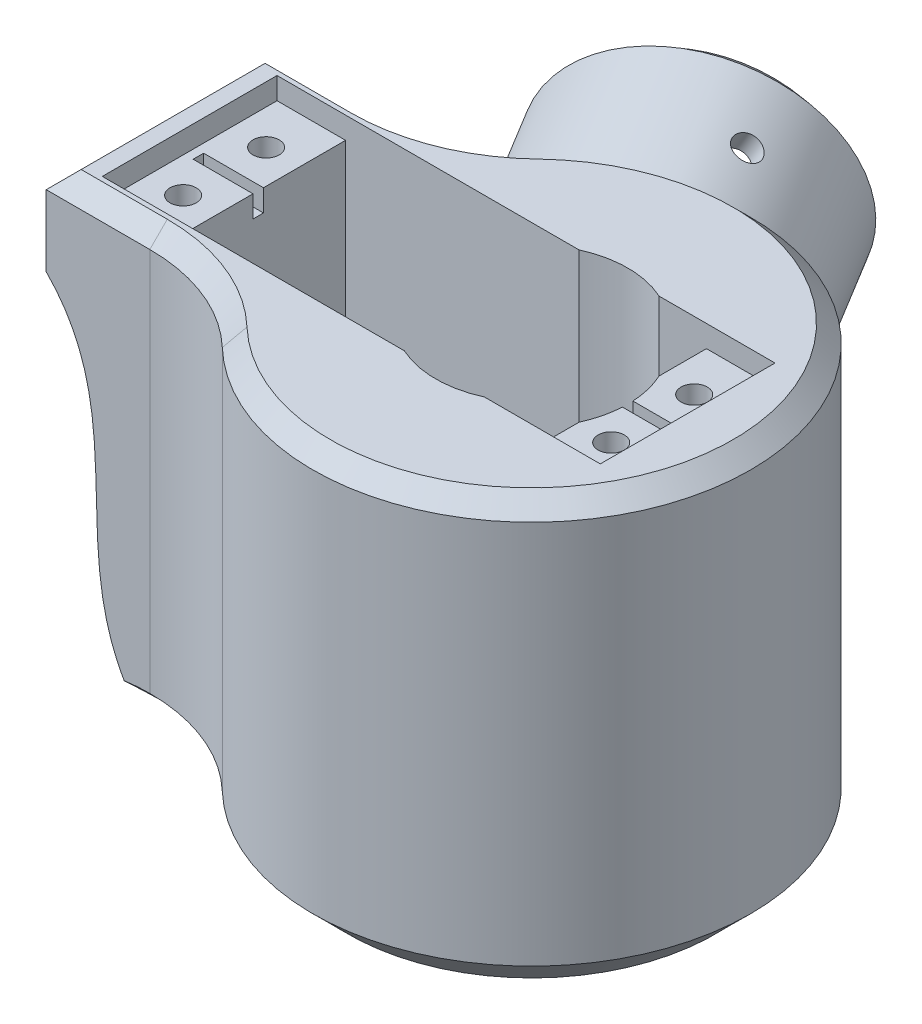
SolidWorks part; units mm, degrees
material "Melamine resin"
ref_plane "Front Plane" through (0, 0, 0) normal (0, 0, 1) x (1, 0, 0)
ref_plane "Top Plane" through (0, 0, 0) normal (0, 1, 0) x (1, 0, 0)
ref_plane "Right Plane" through (0, 0, 0) normal (1, 0, 0) x (0, 0, -1)
sketch "Sketch1" plane through (0, 0, 0) normal (0, 1, 0) x (1, 0, 0)
  line L0 (-37, -12.5248) -> (-25.1408, -12.5248)
  line L1 (-37, -12.5248) -> (-37, 12.5248)
  line L2 (-37, 12.5248) -> (-25.1408, 12.5248)
  arc A0 (-11.2801, -18.0914) -> (-25.1408, -12.5248) centre (-25.1408, -32.5646) ccw
  arc A1 (-25.1408, 12.5248) -> (-11.2801, 18.0914) centre (-25.1408, 32.5646) ccw
  arc A2 (-11.2801, -18.0914) -> (-11.2801, 18.0914) centre (6.0458, 0) ccw
  dimension "D2" = 20.0397
  dimension "D3" = 25.0497
  dimension "D1" = 37
  dimension "D4" = 6.0458
extrude "Boss-Extrude2" add sketch "Sketch1" along normal blind 50
ref_axis "Axis1" through (6.0458, 50, 0) along (0, -1, 0)
ref_point "Point1"
ref_plane "Plane1" through (0, 25, 0) normal (0, 1, 0) x (1, 0, 0)
sketch "Sketch2" plane through (0, 25, 0) normal (0, 1, 0) x (1, 0, 0)
  point P0 (6.0458, 0)
sketch3d "3DSketch2"
  line L0 (6.0458, 25, 0) -> (-125.4586, 70.8173, -246.2467)
chamfer "Chamfer1" distance 2 angle 45 5 edges at (-17.6724, 50, 13.9685) (-17.6724, 50, -13.9685) (31.0955, 50, 0) (-31.0704, 50, 12.5248) (-31.0704, 50, -12.5248)
sketch3d "3DSketch1"
  line L0 (6.0458, 25, 0) -> (-9.6875, 5.6459, 90)
  line L1 (6.0338, 25, 0) -> (-25.4087, -13.7083, 180) construction
ref_plane "Plane2" through (6.0458, 25, 0) normal (-0.4649, 0.162, -0.8705) x (-0.8854, -0.0758, 0.4587)
sketch "Sketch3" plane through (6.0458, 25, 0) normal (-0.4649, 0.162, -0.8705) x (-0.8854, -0.0758, 0.4587)
  circle A0 centre (0, 0) radius 15
  dimension "D1" = 30
extrude "Boss-Extrude3" add sketch "Sketch3" along normal blind 50
sketch "Sketch5" plane through (-23.8183, 8.2985, -44.6006) normal (-0.4649, 0.162, -0.8705) x (-0.8767, -0.2212, 0.4271)
  circle A0 centre (-10.8312, 23.296) radius 12.7
  dimension "D1" = 25.4
extrude "Cut-Extrude1" cut sketch "Sketch5" against normal blind 21
fillet "Fillet2" radius 3 2 edges at (-16.6363, 28.2884, -10.6306) (-17.5453, 23.9713, -14.02)
chamfer "Chamfer2" distance 3 angle 45 1 edges at (-30.4282, 33.0979, -36.4564)
ref_plane "Plane3" through (-37, 48, -12.5248) normal (0.4917, 0.8648, -0.1017) x (0.8707, -0.4872, 0.0669)
sketch "Sketch6" plane through (-37, 48, -12.5248) normal (0.4917, 0.8648, -0.1017) x (0.8707, -0.4872, 0.0669)
  line L0 (24.0545, 30.2209) -> (44.8977, -2.1034) construction
  line L1 (36.6609, 38.3497) -> (11.448, 22.092) construction
  line L2 (49.5248, -9.2792) -> (-103.7829, 228.4745) construction
  circle A0 centre (28.3898, 23.4975) radius 1.5
  dimension "D1" = 3
  dimension "D2" = 8
extrude "Cut-Extrude2" cut sketch "Sketch6" against normal mid plane 40
ref_point "Point2"
sketch "Sketch7" plane through (0, 0, 0) normal (0, -1, 0) x (-1, 0, 0)
  circle A0 centre (-6.0458, 0) radius 4.125
  dimension "D1" = 8.25
extrude "Cut-Extrude3" cut sketch "Sketch7" against normal blind 117
sketch "Sketch8" plane through (0, 0, 0) normal (0, -1, 0) x (1, 0, 0)
  circle A0 centre (6.0458, 0) radius 11
  dimension "D1" = 22
extrude "Cut-Extrude4" cut sketch "Sketch8" against normal blind 8
sketch "Sketch9" plane through (0, 0, -12.5248) normal (0, 0, -1) x (-1, 0, 0)
  line L0 (37, 48) -> (37, 0) construction
  line L1 (25.1408, 0) -> (37, 0)
  line L2 (37, 0) -> (37, 39.8592)
  line L3 (37, 48) -> (25.1408, 48) construction
  spline S0 degree 3 poles (25.1408, 0) (36.5072, 11.2641) (26.1211, 28.9323) (37, 39.8592) knots 0 0 0 0 1 1 1 1
  dimension "D1" = 4.2177
  dimension "D2" = 6.1294
  dimension "D3" = 8.1408
  dimension "D4" = 15.0833
  dimension "D5" = 34.9044
extrude "Cut-Extrude5" cut sketch "Sketch9" against normal blind 96
chamfer "Chamfer3" distance 2 angle 45 1 edges at (-37, 50, 0)
sketch "Sketch10" plane through (0, 50, 0) normal (0, 1, 0) x (1, 0, 0)
  line L0 (22.894, 0) -> (-44.1666, 0) construction
  line L1 (16.0458, 10) -> (-25.2578, 10)
  line L2 (16.0458, 10) -> (16.0458, -10)
  line L3 (16.0458, -10) -> (-25.2578, -10)
  line L4 (-25.2578, 10) -> (-25.2578, -10)
  line L5 (16.0458, 10) -> (-25.2578, -10) construction
  line L6 (16.0458, -10) -> (-25.2578, 10) construction
  line L7 (-32.106, 10) -> (22.894, 10)
  line L8 (-32.106, 10) -> (-32.106, -10)
  line L9 (-32.106, -10) -> (22.894, -10)
  line L10 (22.894, 10) -> (22.894, -10)
  line L11 (-32.106, 10) -> (22.894, -10) construction
  line L12 (-32.106, -10) -> (22.894, 10) construction
  line L13 (-4.606, 0) -> (-4.606, -13.0522) construction
  line L14 (9.1976, 0.6) -> (22.894, 0.6)
  line L15 (9.1976, 0.6) -> (9.1976, -0.6)
  line L16 (9.1976, -0.6) -> (22.894, -0.6)
  line L17 (22.894, 0.6) -> (22.894, -0.6)
  line L18 (9.1976, 0.6) -> (22.894, -0.6) construction
  line L19 (9.1976, -0.6) -> (22.894, 0.6) construction
  line L20 (-4.606, -13.0522) -> (-4.606, 13.6107) construction
  line L21 (-32.106, 10) -> (-32.106, -10)
  line L22 (-18.4096, 0.6) -> (-18.4096, -0.6)
  line L23 (-18.4096, -0.6) -> (-32.106, -0.6)
  line L24 (-18.4096, 0.6) -> (-32.106, 0.6)
  circle A0 centre (19.894, -4.75) radius 1.5
  circle A1 centre (19.894, 4.75) radius 1.5
  circle A2 centre (-29.106, -4.75) radius 1.5
  circle A3 centre (-29.106, 4.75) radius 1.5
  point P0 (4.5863, -4.4511)
  point P6 (-4.606, 0)
  point P12 (16.0458, 0)
  circle M17 centre (6.0458, 0) radius 4.125
  dimension "D6" = 3
  dimension "D1" = 20
  dimension "D2" = 41.3036
  dimension "D3" = 10
  dimension "D4" = 55
  dimension "D5" = 1.2
  dimension "D7" = 5.25
  dimension "D8" = 3
extrude "Cut-Extrude6" cut sketch "Sketch10" against normal blind 35 contours L24 L22 L23 L4 L3 L2 L16 L14 L1 M17 | L22 L24 L4 L23 | A3 | A2 | L16 L2 L14 M17 | A0 | A1 region at (-5.3362, 50, 0) region at (13.101, 50, 0) region at (-21.8337, 50, 0) region at (19.894, 50, 4.75) region at (19.894, 50, -4.75) region at (-29.106, 50, 4.75) region at (-29.106, 50, -4.75)
sketch "Sketch11" plane through (0, 50, 0) normal (0, 1, 0) x (1, 0, 0)
  line L0 (-35, 10.5248) -> (-35, -10.5248) construction
  line L1 (22.894, -0.6) -> (16.0458, -0.6)
  line L2 (22.894, -0.6) -> (22.894, 0.6)
  line L3 (22.894, 0.6) -> (16.0458, 0.6)
  line L4 (16.0458, -0.6) -> (16.0458, 0.6)
  line L5 (-32.106, -0.6) -> (-25.2578, -0.6)
  line L6 (-32.106, -0.6) -> (-32.106, 0.6)
  line L7 (-32.106, 0.6) -> (-25.2578, 0.6)
  line L8 (-25.2578, -0.6) -> (-25.2578, 0.6)
  line L9 (-25.1408, 10.5248) -> (-35, 10.5248) construction
  dimension "D1" = 9.8592
extrude "Cut-Extrude7" cut sketch "Sketch11" against normal blind 5
sketch "Sketch12" plane through (0, 50, 0) normal (0, 1, 0) x (1, 0, 0)
  line L0 (16.0458, -10) -> (-25.2578, -10) construction
  line L1 (23.894, 10) -> (-33.106, 10)
  line L2 (23.894, 10) -> (23.894, -10)
  line L3 (23.894, -10) -> (-33.106, -10)
  line L4 (-33.106, 10) -> (-33.106, -10)
  line L5 (16.0458, 10) -> (-25.2578, 10) construction
  line L8 (22.894, -0.6) -> (22.894, 0.6) construction
  line L9 (-32.106, 0.6) -> (-32.106, -0.6) construction
  dimension "D1" = 1
  dimension "D2" = 1
extrude "Cut-Extrude8" cut sketch "Sketch12" against normal blind 2.5
sketch "Sketch13" plane through (0, 15, 0) normal (0, 1, 0) x (1, 0, 0)
  circle A0 centre (6.0458, 0) radius 11
  dimension "D1" = 22
extrude "Cut-Extrude9" cut sketch "Sketch13" against normal blind 2.5 and the other way blind 43
chamfer "Chamfer4" distance 4 angle 45 3 edges at (-17.6724, 0, 13.9685) (-17.6724, 0, -13.9685) (31.0955, 0, 0)
